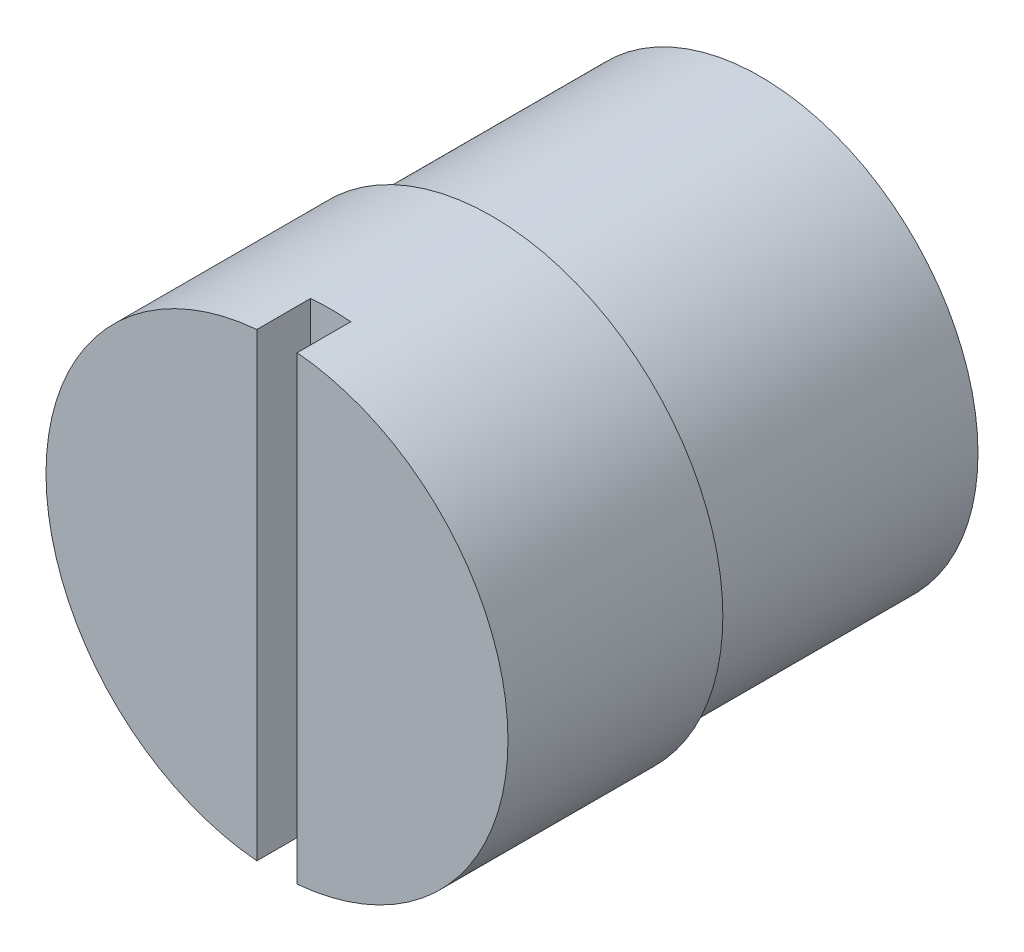
SolidWorks part; units mm, degrees
ref_plane "Front Plane" through (0, 0, 0) normal (0, 0, 1) x (1, 0, 0)
ref_plane "Top Plane" through (0, 0, 0) normal (0, 1, 0) x (1, 0, 0)
ref_plane "Right Plane" through (0, 0, 0) normal (1, 0, 0) x (0, 0, -1)
sketch "Sketch1" plane through (0, 0, 0) normal (0, 0, 1) x (1, 0, 0)
  circle A0 centre (0, 0) radius 2.55 construction
  circle A3 centre (0, 0) radius 2.35 construction
  circle A4 centre (0, 0) radius 4.05
  dimension "D1" = 4.7
  dimension "D2" = 0.2
  dimension "D3" = 1.5
extrude "Boss-Extrude1" add sketch "Sketch1" against normal blind 5
sketch "Sketch2" plane through (0, 0, 0) normal (0, 0, 1) x (1, 0, 0)
  circle A2 centre (0, 0) radius 4.3
  circle A3 centre (0, 0) radius 4.3
  dimension "D1" = 0.25
extrude "Boss-Extrude2" add sketch "Sketch2" along normal blind 4
sketch "Sketch4" plane through (0, 0, -5) normal (0, 0, -1) x (-1, 0, 0)
  point P0 (0, 0)
hole_wizard "M5x0.8 Tapped Hole1" positions "Sketch4" profile "Sketch6" tap size "M5x0.8" standard "ANSI Metric"
sketch "Sketch6" plane through (0, 0, -5) normal (1, 0, 0) x (0, 1, 0)
  line L0 (0, 0) -> (0, 5)
  line L1 (0, 5) -> (2.215, 5)
  line L2 (2.215, 5) -> (2.215, 0)
  line L5 (2.215, 0) -> (0, 0)
  line L10 (0, 5) -> (-2.215, 5) construction
  line L11 (0, -6.35) -> (0, 107.95) construction
  dimension "Tap Drill Dia." = 4.43
  dimension "Tap Drill Depth" = 5
  dimension "Drill Angle" = 180
chamfer "Chamfer1" distance 0.75 angle 45 1 edges at (-2.215, 0, -5)
thread "Thread1" pitch 1 method cut profile "Thread Profile1" start angle 0, offset 1, length 5.5, pitch 1, diameter 4.43
ref_plane "Plane1" through (2.215, 0, -6) normal (0, -1, 0) x (1, 0, 0)
sketch "Thread Profile1" plane through (2.215, 0, -6) normal (0, -1, 0) x (1, 0, 0)
  line L0 (0, 0) -> (0, 1) construction
  line L1 (0, 0) -> (0.5413, 0.3125)
  line L2 (0.5413, 0.3125) -> (0.5413, 0.4375)
  line L3 (0.5413, 0.4375) -> (0, 0.75)
  line L4 (0.5413, 0.375) -> (0, 0.375) construction
  line L11 (0, 0) -> (0, 0.75)
  point P2 (0, 0)
  dimension "Pitch" = 1
  dimension "Profile_Angle" = 60
  dimension "Profile_Land" = 0.125
  dimension "Profile_Height" = 0.5413
sketch "Sketch3" plane through (0, 0, 4) normal (0, 0, 1) x (1, 0, 0)
  line L0 (0, 4.3) -> (0, -4.3) construction
  line L1 (-0.375, -4.3) -> (0.375, -4.3)
  line L2 (-0.375, 4.3) -> (0.375, 4.3)
  line L3 (0.375, -4.3) -> (0.375, 4.3)
  line L4 (-0.375, 4.3) -> (-0.375, -4.3)
  circle A0 centre (0, 0) radius 4.3 construction
  point P7 (0, 0)
  point P11 (0, -4.3)
  point P14 (0, 4.3)
  dimension "D1" = 0.75
extrude "Cut-Extrude1" cut sketch "Sketch3" against normal blind 1
equation "\"ThreadWalls\"= 1.5"
equation "\"D3@Sketch1\"=\"ThreadWalls\""
equation "\"BaseFlange\"= 0.25"
equation "\"D1@Sketch2\"=\"BaseFlange\""
